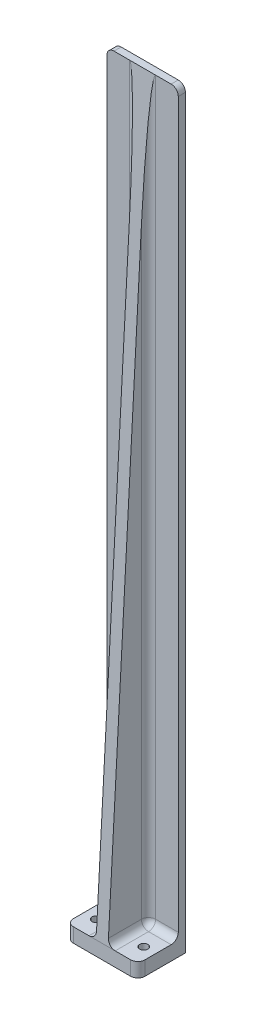
SolidWorks part; units mm, degrees
material "ABS"
ref_plane "前视基准面" through (0, 0, 0) normal (0, 0, 1) x (1, 0, 0)
ref_plane "上视基准面" through (0, 0, 0) normal (0, 1, 0) x (1, 0, 0)
ref_plane "右视基准面" through (0, 0, 0) normal (1, 0, 0) x (0, 0, -1)
other "Configuration Table"
sketch "草图1" plane through (0, 0, 0) normal (0, 1, 0) x (1, 0, 0)
  line L0 (-15, -2.5) -> (15, -2.5) construction
  line L1 (-15, -10) -> (15, -10)
  line L2 (-15, -10) -> (-15, 10)
  line L3 (-15, 10) -> (15, 10)
  line L4 (15, -10) -> (15, 10)
  line L5 (-15, -10) -> (15, 10) construction
  line L6 (-15, 10) -> (15, -10) construction
  line L7 (0, 0) -> (0, 10) construction
  circle A0 centre (-10, -2.5) radius 1.75
  circle A1 centre (10, -2.5) radius 1.75
  point P0 (0, 0)
  dimension "D4" = 20
  dimension "D5" = 3.5
  dimension "D1" = 20
  dimension "D2" = 30
  dimension "D3" = 7.5
extrude "凸台-拉伸1" add sketch "草图1" along normal blind 6
sketch "草图2" plane through (15, 0, 0) normal (1, 0, 0) x (0, 0, -1)
  line L1 (10, 6) -> (7, 6)
  line L2 (10, 6) -> (10, 316)
  line L3 (10, 316) -> (7, 316)
  line L4 (7, 6) -> (7, 316)
  dimension "D1" = 3
  dimension "D2" = 310
extrude "凸台-拉伸2" add sketch "草图2" against normal blind 30
sketch "草图3" plane through (0, 0, 0) normal (1, 0, 0) x (0, 0, -1)
  line L0 (7, 316) -> (-10, 6)
  line L1 (-10, 6) -> (7, 6)
  line L2 (7, 6) -> (7, 316)
extrude "凸台-拉伸3" add sketch "草图3" along normal mid plane 5
fillet "圆角1" radius 3 10 edges at (-15, 316, -8.5) (15, 316, -8.5) (15, 3, 10) (-15, 3, 10) (8.75, 6, -7) (2.5, 161, -7) (2.5, 6, 1.5) (-2.5, 6, 1.5) (-2.5, 161, -7) (-8.75, 6, -7)
